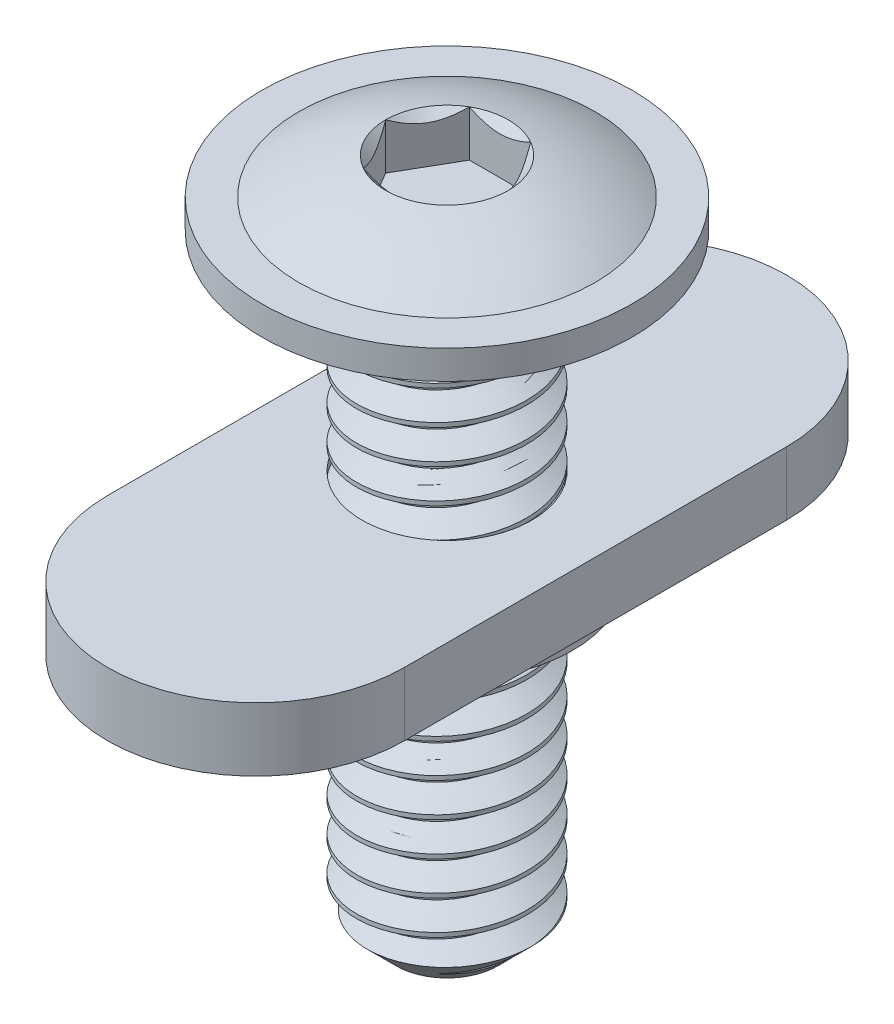
SolidWorks part; units mm, degrees
ref_plane "Front Plane" through (0, 0, 0) normal (0, 0, 1) x (1, 0, 0)
ref_plane "Top Plane" through (0, 0, 0) normal (0, 1, 0) x (1, 0, 0)
ref_plane "Right Plane" through (0, 0, 0) normal (1, 0, 0) x (0, 0, -1)
sketch "Sketch1" plane through (0, 0, 0) normal (0, 0, 1) x (1, 0, 0)
  line L0 (0, 0) -> (0, 53.1234) construction
  line L1 (0, 0) -> (-3.175, 0)
  line L2 (-3.175, 0) -> (-3.175, 12.7)
  line L3 (-3.175, 12.7) -> (-6.9215, 12.7)
  line L4 (-6.9215, 12.7) -> (-6.9215, 13.777)
  line L5 (-6.9215, 13.777) -> (-5.5372, 13.777)
  line L6 (0, 0) -> (0, 15.3924)
  arc A0 (-5.5372, 13.777) -> (0, 15.3924) centre (0, 5.0948) cw
  dimension "screw od" = 6.35
  dimension "head od" = 13.843
  dimension "D3" = 11.0744
  dimension "D4" = 1.077
  dimension "head height" = 2.6924
  dimension "screw length" = 12.7
sketch "Sketch2" plane through (0, 0, 0) normal (0, 0, 1) x (1, 0, 0)
  line L1 (-3.175, 12.7) -> (-6.9215, 12.7) construction
  line L4 (0, -10.16) -> (0, 12.7)
  line L5 (0, 12.7) -> (-3.175, 12.7)
  line L6 (0, -10.16) -> (-3.175, -10.16)
  line L7 (-3.175, -10.16) -> (-3.175, 12.7)
revolve "Revolve2" add sketch "Sketch2" angle 360 about L0
sketch "Sketch3" plane through (0, 12.7, 0) normal (0, 1, 0) x (1, 0, 0)
  circle A1 centre (0, 0) radius 3.175
  circle A2 centre (0, 0) radius 3.175
  dimension "D1" = 0
curve "Helix/Spiral1" pitch 1.27 height 25.4 turns 20 parameters "pitch"=1.27
chamfer "Chamfer1" distance 1.27 angle 45 1 edges at (0, -10.16, -3.175)
sketch "Sketch4" plane through (0, 0, 0) normal (0, 0, 1) x (1, 0, 0)
  line L0 (3.175, 13.8112) -> (3.175, 12.7)
  line L1 (3.175, 12.7) -> (2.3501, 13.1762)
  line L2 (2.3501, 13.1762) -> (2.3501, 13.335)
  line L3 (2.3501, 13.335) -> (3.175, 13.8112)
  line L4 (2.3501, 13.2556) -> (3.175, 13.2556) construction
  line L5 (2.7626, 12.9381) -> (2.7626, 13.5731) construction
  line L7 (3.175, 12.7) -> (-3.175, 12.7) construction
  dimension "D1" = 60
  dimension "D2" = 0.1588
  dimension "D3" = 0.635
sweep "Cut-Sweep1" cut profiles "Sketch4" path "Helix/Spiral1"
sketch "Sketch5" plane through (0, 0, 0) normal (0, 0, 1) x (1, 0, 0)
  line L0 (0, 0) -> (0, 15.3924) construction
  line L1 (-3.175, 12.7) -> (-6.9215, 12.7) construction
  line L2 (-6.9215, 13.777) -> (-5.5372, 13.777) construction
  line L3 (-6.9215, 12.7) -> (-6.9215, 13.777) construction
  line L4 (0, 12.7) -> (0, 15.3924)
  line L5 (0, 12.7) -> (-6.9215, 12.7)
  line L6 (-6.9215, 13.777) -> (-5.5372, 13.777)
  line L7 (-6.9215, 12.7) -> (-6.9215, 13.777)
  arc A0 (0, 15.3924) -> (-5.5372, 13.777) centre (0, 5.0948) ccw construction
  arc A1 (0, 15.3924) -> (-5.5372, 13.777) centre (0, 5.0948) ccw
revolve "Revolve3" add sketch "Sketch5" angle 360 about L0
ref_plane "Plane1" through (0, 15.3924, 0) normal (0, 1, 0) x (-1, 0, 0)
sketch "Sketch6" plane through (0, 15.3924, 0) normal (0, 1, 0) x (-1, 0, 0)
  line L1 (1.1457, 1.9844) -> (-1.1457, 1.9844)
  line L2 (-1.1457, 1.9844) -> (-2.2914, 0)
  line L3 (-2.2914, 0) -> (-1.1457, -1.9844)
  line L4 (-1.1457, -1.9844) -> (1.1457, -1.9844)
  line L5 (1.1457, -1.9844) -> (2.2914, 0)
  line L6 (2.2914, 0) -> (1.1457, 1.9844)
  circle A0 centre (0, 0) radius 1.9844 construction
  dimension "hex" = 3.9688
extrude "Cut-Extrude1" cut sketch "Sketch6" against normal blind 1.9844
ref_plane "Plane2" through (0, 15.1342, 0) normal (0, 1, 0) x (-1, 0, 0)
sketch "Sketch7" plane through (0, 15.1342, 0) normal (0, 1, 0) x (-1, 0, 0)
  circle A0 centre (0, 0) radius 2.2914
extrude "Cut-Extrude2" cut sketch "Sketch7" against normal up to surface (1.7262 mm away) draft 45 and the other way through all
ref_plane "Plane3" through (0, 3.175, 0) normal (0, -1, 0) x (1, 0, 0)
sketch "Sketch8" plane through (0, 3.175, 0) normal (0, -1, 0) x (1, 0, 0)
  line L0 (0, -7.1437) -> (0, 7.1437) construction
  line L2 (-5.5563, 7.1437) -> (-5.5563, -7.1437)
  line L4 (5.5563, 7.1437) -> (5.5563, -7.1437)
  circle A0 centre (0, 0) radius 3.175
  arc A1 (-5.5563, 7.1437) -> (5.5563, 7.1437) centre (0, 7.1437) cw
  arc A2 (-5.5563, -7.1437) -> (5.5563, -7.1437) centre (0, -7.1437) ccw
  dimension "D1" = 6.35
  dimension "D3" = 25.4
  dimension "D2" = 11.1125
extrude "Extrude1" add sketch "Sketch8" along normal mid plane 3.4544 separate body
sketch "Sketch9" plane through (0, 1.4478, 0) normal (0, -1, 0) x (1, 0, 0)
  line L2 (5.5563, -7.1437) -> (5.5563, 7.1437)
  line L3 (-5.5563, 7.1437) -> (-5.5563, -7.1437)
  line L4 (5.5563, -7.1437) -> (5.5563, 7.1437)
  line L5 (-5.5563, 7.1437) -> (-5.5563, -7.1437)
  arc A2 (-5.5563, -7.1437) -> (5.5563, -7.1437) centre (0, -7.1437) ccw
  arc A3 (5.5563, 7.1437) -> (-5.5563, 7.1437) centre (0, 7.1437) ccw
  arc A4 (-5.5563, -7.1437) -> (5.5563, -7.1437) centre (0, -7.1437) ccw
  arc A5 (5.5563, 7.1437) -> (-5.5563, 7.1437) centre (0, 7.1437) ccw
  circle A6 centre (0, 0) radius 4.699
  circle A7 centre (0, 0) radius 4.699
  dimension "D1" = 0
  dimension "D2" = 1.524
extrude "Cut-Extrude3" cut sketch "Sketch9" against normal offset from surface (1.0795 mm away) 2.3749 up to face at (0, 4.9022, 0)
sketch "Sketch10" [suppressed] plane through (0, 7.9375, 0) normal (0, -1, 0) x (1, 0, 0)
  line L0 (-8.255, -12.3888) -> (-8.255, 2.8511)
  line L1 (8.255, 2.8511) -> (8.255, -12.3888)
  line L2 (-14.9844, 7.9311) -> (0, 7.9311) construction
  circle A0 centre (0, 0) radius 3.9688
  arc A1 (8.255, 2.8511) -> (-8.255, 2.8511) centre (0, -1.316) ccw
  arc A2 (-8.255, -12.3888) -> (8.255, -12.3888) centre (0, -8.2217) ccw
  dimension "D2" = 3.9624
  dimension "D3" = 16.51
  dimension "D4" = 5.08
  dimension "D5" = 6.35
  dimension "D1" = 25.4
extrude "Extrude2" [suppressed] add sketch "Sketch10" along normal mid plane 5.3594 separate body
sketch "Sketch11" [suppressed] plane through (0, 5.2578, 0) normal (0, -1, 0) x (1, 0, 0)
  line L2 (8.255, -12.3888) -> (8.255, 2.8511)
  line L3 (-8.255, 2.8512) -> (-8.255, -12.3888)
  line L4 (8.255, -12.3888) -> (8.255, 2.8511)
  line L5 (-8.255, 2.8512) -> (-8.255, -12.3888)
  circle A2 centre (0, 0) radius 5.4927
  circle A3 centre (0, 0) radius 5.4927
  arc A5 (-8.255, -12.3888) -> (8.255, -12.3888) centre (0, -8.2217) ccw
  arc A6 (8.255, 2.8511) -> (-8.255, 2.8512) centre (0, -1.316) ccw
  arc A7 (-8.255, -12.3888) -> (8.255, -12.3888) centre (0, -8.2217) ccw
  arc A8 (8.255, 2.8511) -> (-8.255, 2.8512) centre (0, -1.316) ccw
  dimension "D1" = 1.524
  dimension "D2" = 0
extrude "Cut-Extrude4" [suppressed] cut sketch "Sketch11" against normal offset from surface (1.651 mm away) 3.7084
sketch "Sketch12" [suppressed] plane through (0, 0, 0) normal (0, 0, 1) x (1, 0, 0)
  line L0 (-6.7564, 17.78) -> (-5.4051, 17.78) construction
  line L1 (-6.7564, 17.78) -> (-5.4051, 17.78)
  line L2 (10.3378, 20.0315) -> (-10.3378, 20.0315) construction
  line L3 (0, 0) -> (0, 53.1234) construction
  line L4 (-3.9688, 15.875) -> (-6.7564, 15.875) construction
  line L5 (-9.398, 15.875) -> (-3.9688, 15.875)
  line L6 (-9.398, 15.875) -> (-9.398, 14.605)
  line L7 (-9.398, 14.605) -> (-3.9688, 14.605)
  line L8 (-3.9688, 15.875) -> (-3.9688, 14.605)
  arc A0 (0, 20.6375) -> (-5.4051, 17.78) centre (0, 14.0967) ccw construction
  arc A1 (-2.7496, 20.0315) -> (-5.4051, 17.78) centre (0, 14.0967) ccw
  arc A2 (-6.7564, 17.78) -> (-2.7496, 20.0315) centre (0, 10.4472) cw
  dimension "D1" = 9.398
  dimension "D2" = 1.27
revolve "Revolve4" [suppressed] add sketch "Sketch12" angle 360 about L0
sketch "Sketch13" [suppressed] plane through (0, 6.35, 0) normal (0, -1, 0) x (1, 0, 0)
  line L0 (-7.9375, 4.7562) -> (-7.9375, -17.4688)
  line L1 (7.9375, 4.7562) -> (7.9375, -17.4688)
  circle A0 centre (0, 0) radius 3.9688
  arc A1 (-7.9375, 4.7562) -> (7.9375, 4.7562) centre (0, -3.5782) cw
  arc A2 (-7.9375, -17.4688) -> (7.9375, -17.4688) centre (0, -9.1345) ccw
  dimension "D2" = 28.575
  dimension "D3" = 3.9624
  dimension "D4" = 7.9375
  dimension "D1" = 15.875
  dimension "D5" = 3.175
extrude "Extrude4" [suppressed] add sketch "Sketch13" along normal mid plane 5.8928 separate body
sketch "Sketch14" [suppressed] plane through (0, 3.4036, 0) normal (0, -1, 0) x (1, 0, 0)
  line L2 (-7.9375, 4.7561) -> (-7.9375, -17.4688)
  line L3 (7.9375, -17.4688) -> (7.9375, 4.7562)
  line L4 (-7.9375, 4.7561) -> (-7.9375, -17.4688)
  line L5 (7.9375, -17.4688) -> (7.9375, 4.7562)
  arc A2 (7.9375, 4.7562) -> (-7.9375, 4.7561) centre (0, -3.5782) ccw
  arc A3 (-7.9375, -17.4688) -> (7.9375, -17.4688) centre (0, -9.1345) ccw
  arc A4 (7.9375, 4.7562) -> (-7.9375, 4.7561) centre (0, -3.5782) ccw
  arc A5 (-7.9375, -17.4688) -> (7.9375, -17.4688) centre (0, -9.1345) ccw
  circle A6 centre (0, 0) radius 5.4927
  circle A7 centre (0, 0) radius 5.4927
  dimension "D1" = 0
  dimension "D2" = 1.524
extrude "Cut-Extrude7" [suppressed] cut sketch "Sketch14" against normal offset from surface (1.8034 mm away) 4.0894
sketch "Sketch15" [suppressed] plane through (0, 0, 0) normal (0, 0, 1) x (1, 0, 0)
  line L0 (-6.6675, 19.6774) -> (-5.334, 19.6774) construction
  line L1 (-6.6675, 19.6774) -> (-5.334, 19.6774)
  line L2 (9.2481, 22.5402) -> (-9.2481, 22.5402) construction
  line L3 (0, 0) -> (0, 53.1234) construction
  arc A0 (0, 22.9997) -> (-5.334, 19.6774) centre (0, 17.0567) ccw construction
  arc A1 (-2.2914, 22.5402) -> (-5.334, 19.6774) centre (0, 17.0567) ccw
  arc A2 (-2.2914, 22.5402) -> (-6.6675, 19.6774) centre (0, 14.2615) ccw
revolve "Revolve5" [suppressed] add sketch "Sketch15" angle 360 about L0
sketch "Sketch16" [suppressed] plane through (0, 3.175, 0) normal (0, -1, 0) x (1, 0, 0)
  line L0 (-6.3881, 8.443) -> (-6.3881, -33.843)
  line L1 (6.3881, 8.443) -> (6.3881, -33.843)
  line L2 (0, -25.4) -> (0, 0) construction
  line L3 (0, -12.7) -> (-6.3881, -12.7) construction
  line L4 (-6.3881, -27.1355) -> (-6.3881, 1.7355) construction
  circle A0 centre (0, 0) radius 3.175
  circle A1 centre (0, -25.4) radius 3.175
  arc A2 (-6.3881, 8.443) -> (6.3881, 8.443) centre (0, 1.7355) cw
  arc A3 (-6.3881, -33.843) -> (6.3881, -33.843) centre (0, -27.1355) ccw
  dimension "D1" = 25.4
  dimension "D2" = 6.35
  dimension "D4" = 47.3964
  dimension "D3" = 12.7762
  dimension "D5" = 2.5552
extrude "Extrude5" [suppressed] add sketch "Sketch16" along normal mid plane 4.0894 separate body
sketch "Sketch17" [suppressed] plane through (0, 1.1303, 0) normal (0, -1, 0) x (1, 0, 0)
  line L2 (-6.3881, 8.443) -> (-6.3881, -33.843)
  line L3 (6.3881, -33.843) -> (6.3881, 8.443)
  line L4 (-6.3881, 8.443) -> (-6.3881, -33.843)
  line L5 (6.3881, -33.843) -> (6.3881, 8.443)
  arc A2 (6.3881, 8.443) -> (-6.3881, 8.443) centre (0, 1.7355) ccw
  arc A3 (-6.3881, -33.843) -> (6.3881, -33.843) centre (0, -27.1355) ccw
  arc A4 (6.3881, 8.443) -> (-6.3881, 8.443) centre (0, 1.7355) ccw
  arc A5 (-6.3881, -33.843) -> (6.3881, -33.843) centre (0, -27.1355) ccw
  circle A6 centre (0, -25.4) radius 4.699
  circle A7 centre (0, -25.4) radius 4.699
  circle A10 centre (0, 0) radius 4.699
  circle A11 centre (0, 0) radius 4.699
  dimension "D1" = 0
  dimension "D2" = 1.524
  dimension "D3" = 1.524
pattern_linear "LPattern1" [suppressed] count 2 spacing 25.4
extrude "Cut-Extrude9" [suppressed] cut sketch "Sketch17" against normal offset from surface (1.4224 mm away) 2.667
sketch "Sketch18" [suppressed] plane through (0, 7.9375, 0) normal (0, -1, 0) x (1, 0, 0)
  line L0 (-7.9375, 13.462) -> (-7.9375, -51.562)
  line L1 (7.9375, 13.462) -> (7.9375, -51.562)
  line L2 (0, 0) -> (0, -38.1) construction
  line L3 (0, -19.05) -> (-7.9375, -19.05) construction
  line L4 (0, -19.05) -> (7.9375, -19.05) construction
  circle A0 centre (0, 0) radius 3.9688
  circle A1 centre (0, -38.1) radius 3.9688
  arc A2 (-7.9375, 13.462) -> (7.9375, 13.462) centre (0, 5.1276) cw
  arc A3 (-7.9375, -51.562) -> (7.9375, -51.562) centre (0, -43.2276) ccw
  dimension "D1" = 38.1
  dimension "D2" = 7.9375
  dimension "D4" = 3.175
  dimension "D5" = 71.374
  dimension "D3" = 15.875
extrude "Extrude6" [suppressed] add sketch "Sketch18" along normal mid plane 5.9944 separate body
sketch "Sketch19" [suppressed] plane through (0, 4.9403, 0) normal (0, -1, 0) x (1, 0, 0)
  line L2 (-7.9375, 13.462) -> (-7.9375, -51.562)
  line L3 (7.9375, -51.562) -> (7.9375, 13.462)
  line L4 (-7.9375, 13.462) -> (-7.9375, -51.562)
  line L5 (7.9375, -51.562) -> (7.9375, 13.462)
  arc A2 (7.9375, 13.462) -> (-7.9375, 13.462) centre (0, 5.1276) ccw
  arc A3 (-7.9375, -51.562) -> (7.9375, -51.562) centre (0, -43.2276) ccw
  arc A4 (7.9375, 13.462) -> (-7.9375, 13.462) centre (0, 5.1276) ccw
  arc A5 (-7.9375, -51.562) -> (7.9375, -51.562) centre (0, -43.2276) ccw
  circle A6 centre (0, 0) radius 5.4927
  circle A7 centre (0, 0) radius 5.4927
  circle A9 centre (0, -38.1) radius 5.4928
  circle A10 centre (0, -38.1) radius 5.4928
  dimension "D1" = 0
  dimension "D2" = 1.524
  dimension "D3" = 1.524
extrude "Cut-Extrude10" [suppressed] cut sketch "Sketch19" against normal offset from surface (2.1844 mm away) 3.81
pattern_linear "LPattern2" [suppressed] count 2 spacing 38.1
equation "\"D2@Sketch4\" = \"pitch@Helix/Spiral1\"*.125"
equation "\"D3@Sketch4\" = \"pitch@Helix/Spiral1\"*.5"
equation "\"D3@Helix/Spiral1\" = \"screw length@Sketch1\"+.18750"
equation "\"D1@Chamfer1\" = \"pitch@Helix/Spiral1\""
equation "\"D1@Cut-Extrude1\" = \"hex@Sketch6\"/2"
equation "\"D1@Sketch8\" = \"screw od@Sketch1\""
equation "\"D4@Sketch1\" = \"head height@Sketch1\"/2.5"
equation "\"D3@Sketch1\" = \"head od@Sketch1\"*.8"
equation "\"D5@Sketch10\" = \"screw od@Sketch1\""
equation "\"D4@Sketch10\" = \"D1@Sketch10\"*.2"
equation "\"D5@Sketch13\" = \"D1@Sketch13\"*.2"
equation "\"D5@Sketch16\" = \"D3@Sketch16\"*.2"
equation "\"D4@Sketch18\" = \"D3@Sketch18\"*.2"
